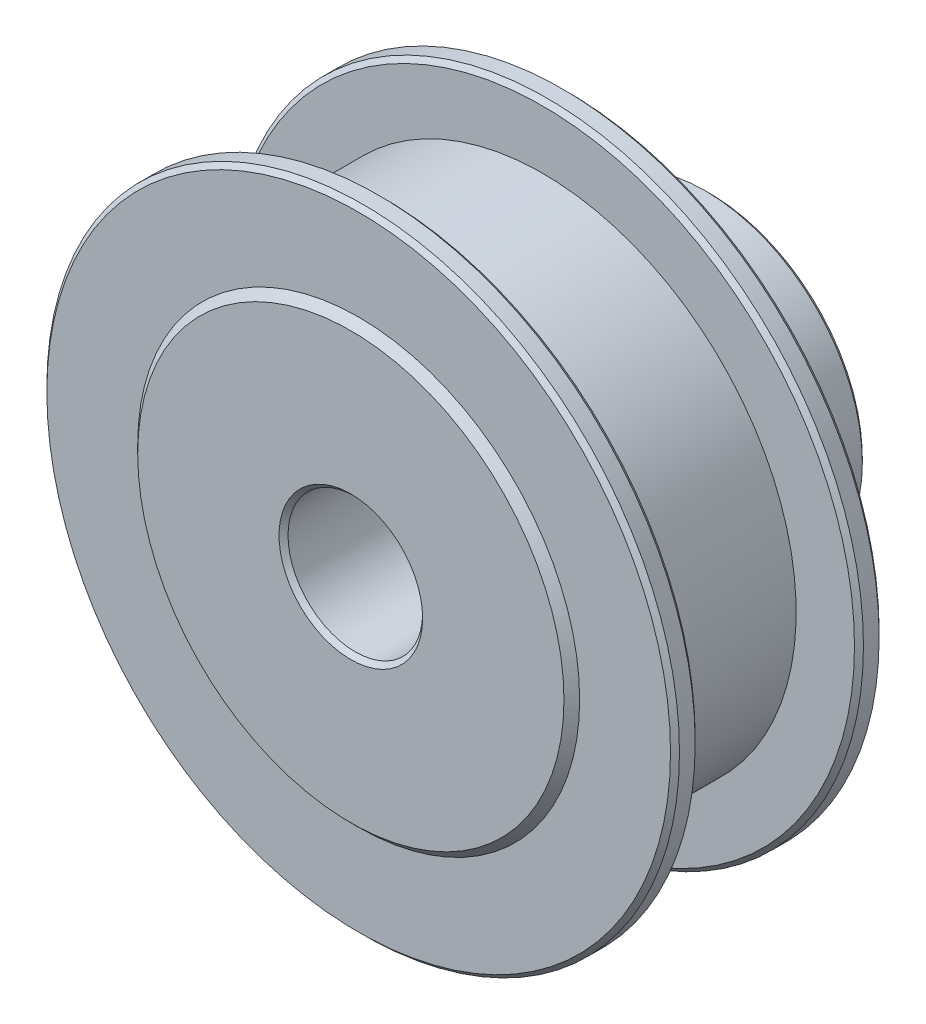
SolidWorks part; units mm, degrees
ref_plane "Front" through (0, 0, 0) normal (0, 0, 1) x (1, 0, 0)
ref_plane "Top" through (0, 0, 0) normal (0, 1, 0) x (1, 0, 0)
ref_plane "Right" through (0, 0, 0) normal (1, 0, 0) x (0, 0, -1)
sketch "Sketch1" plane through (0, 0, 0) normal (0, 0, 1) x (1, 0, 0)
  circle A0 centre (0, 0) radius 14.1
  dimension "D1" = 28.2
extrude "Boss-Extrude1" add sketch "Sketch1" along normal blind 9.3
ref_axis "Axis1" through (0, 0, -195813.9239) along (0, 0, -1)
sketch "Sketch2" plane through (0, 0, 0) normal (1, 0, 0) x (0, 0, -1)
  line L0 (0, 14.1) -> (-9.3, 14.1) construction
  line L1 (-8.2, 14.1) -> (-1.1, 14.1)
  line L2 (-8.2, 14.1) -> (-8.2, 11.3)
  line L3 (-8.2, 11.3) -> (-1.1, 11.3)
  line L4 (-1.1, 14.1) -> (-1.1, 11.3)
  line L5 (-9.3, 14.1) -> (-9.3, -14.1) construction
  line L6 (0, 15.51) -> (0, -15.51) construction
  dimension "D1" = 1.1
  dimension "D2" = 1.1
  dimension "D3" = 2.8
revolve "Cut-Revolve1" cut sketch "Sketch2" angle 360 about axis through (0, 0, -195813.9239) along (0, 0, -1)
sketch "Sketch3" plane through (0, 0, 9.3) normal (0, 0, 1) x (1, 0, 0)
  circle A0 centre (0, 0) radius 9.85
  dimension "D1" = 19.7
extrude "Boss-Extrude2" add sketch "Sketch3" against normal blind 9.65 and the other way blind 0.35
chamfer "Chamfer1" distance 0.35 angle 45 2 edges at (9.85, 0, 9.65) (9.85, 0, -0.35)
sketch "Sketch4" plane through (0, 0, -0.35) normal (0, 0, -1) x (-1, 0, 0)
  circle A0 centre (0, 0) radius 7
  dimension "D1" = 14
extrude "Boss-Extrude3" add sketch "Sketch4" along normal blind 6
sketch "Sketch5" plane through (0, 0, -6.35) normal (0, 0, -1) x (-1, 0, 0)
  circle A0 centre (0, 0) radius 3
  dimension "D1" = 6
extrude "Cut-Extrude1" cut sketch "Sketch5" against normal up to next
chamfer "Chamfer2" distance 0.2 angle 45 7 edges at (-3, 0, -6.35) (3, 0, 9.65) (14.1, 0, 9.3) (-14.1, 0, 8.2) (-14.1, 0, 1.1) (14.1, 0, 0) (-7, 0, -6.35)
